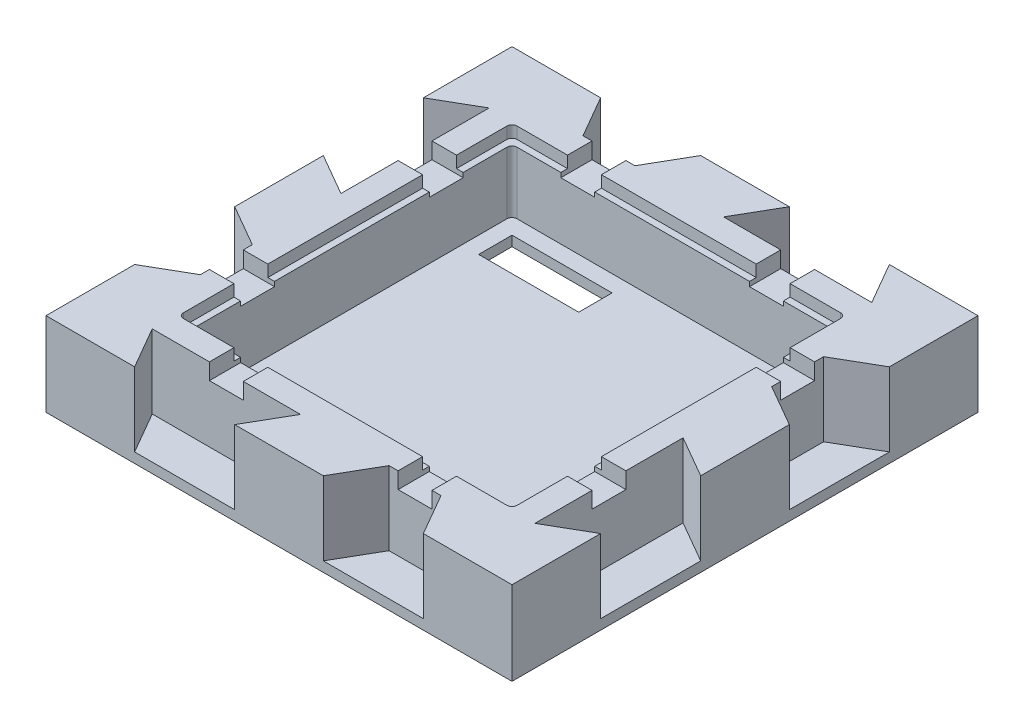
SolidWorks part; units mm, degrees
material "Macor"
ref_plane "Front Plane" through (0, 0, 0) normal (0, 0, 1) x (1, 0, 0)
ref_plane "Top Plane" through (0, 0, 0) normal (0, 1, 0) x (1, 0, 0)
ref_plane "Right Plane" through (0, 0, 0) normal (1, 0, 0) x (0, 0, -1)
sketch "Sketch1" plane through (0, 0, 0) normal (0, 1, 0) x (1, 0, 0)
  line L1 (-69.85, -69.85) -> (69.85, -69.85)
  line L2 (-69.85, -69.85) -> (-69.85, 69.85)
  line L3 (-69.85, 69.85) -> (69.85, 69.85)
  line L4 (69.85, -69.85) -> (69.85, 69.85)
  line L5 (-69.85, -69.85) -> (69.85, 69.85) construction
  line L6 (-69.85, 69.85) -> (69.85, -69.85) construction
  point P0 (0, 0)
  dimension "D1" = 139.7
extrude "Boss-Extrude1" add sketch "Sketch1" along normal mid plane 25.4
sketch "Sketch2" plane through (0, 12.7, 0) normal (0, 1, 0) x (1, 0, 0)
  line L0 (69.85, -69.85) -> (69.85, 69.85) construction
  line L1 (-69.85, -69.85) -> (69.85, -69.85)
  line L2 (-69.85, -69.85) -> (-69.85, 69.85)
  line L3 (-69.85, 69.85) -> (69.85, 69.85)
  line L4 (69.85, -69.85) -> (69.85, 69.85)
  line L5 (-69.85, -69.85) -> (69.85, 69.85) construction
  line L6 (-69.85, 69.85) -> (69.85, -69.85) construction
  point P0 (0, 0)
  dimension "D1" = 0
extrude "Cut-Extrude1" cut sketch "Sketch2" against normal offset from surface (0.3 mm away) 0.3 up to face at (0, 12.7, 0)
sketch "Sketch4" plane through (0, 12.4, 0) normal (0, 1, 0) x (1, 0, 0)
  line L0 (-43.2833, -69.85) -> (-50.5002, -57.35)
  line L2 (-50.5002, -57.35) -> (-6.0665, -57.35)
  line L3 (-6.0665, -57.35) -> (-13.2833, -69.85)
  line L4 (-13.2833, -69.85) -> (-43.2833, -69.85)
  line L5 (43.2833, -69.85) -> (36.0665, -57.35)
  line L24 (43.2833, -69.85) -> (13.2833, -69.85)
  line L25 (-69.85, -69.85) -> (-43.2833, -69.85) construction
  line L26 (-13.2833, -69.85) -> (13.2833, -69.85) construction
  line L27 (43.2833, -69.85) -> (69.85, -69.85) construction
  line L28 (36.0665, -57.35) -> (20.5002, -57.35)
  line L30 (13.2833, -69.85) -> (20.5002, -57.35)
  line L31 (-69.85, 69.85) -> (-69.85, -69.85) construction
  line L32 (69.85, -69.85) -> (69.85, 69.85) construction
  line L33 (-69.85, -69.85) -> (69.85, -69.85) construction
  point P2 (0, 0)
  point P3 (13.2833, -69.85)
  point P7 (0, 0)
  point P11 (0, 0)
  point P12 (0, 0)
  point P13 (0, 0)
  point P14 (-78.8839, -69.85)
  point P19 (0, 0)
  point P22 (80.709, -69.0975)
  point P25 (0, 0)
  dimension "D2" = 30
  dimension "D1" = 60
  dimension "D3" = 12.5
  dimension "D4" = 60
extrude "Cut-Extrude2" cut sketch "Sketch4" against normal offset from surface 3 and the other way through all up to face at (0, -12.7, 0)
sketch "Sketch18" plane through (0, 0, 57.35) normal (0, 0, 1) x (1, 0, 0)
  line L1 (0, -13.805) -> (0, 13.805) construction
  line L3 (23.2033, 12.4) -> (23.2033, 7.525)
  line L4 (23.2033, 7.525) -> (33.3633, 7.525)
  line L5 (33.3633, 12.4) -> (33.3633, 7.525)
  line L6 (-23.2033, 12.4) -> (-33.3633, 12.4)
  line L7 (-33.3633, 12.4) -> (-33.3633, 7.525)
  line L8 (-23.2033, 12.4) -> (-23.2033, 7.525)
  line L9 (-23.2033, 7.525) -> (-33.3633, 7.525)
  line L10 (23.2033, 12.4) -> (33.3633, 12.4)
  line L11 (20.5002, 12.4) -> (36.0665, 12.4) construction
  point P7 (28.2833, 12.4)
  point P14 (28.2833, 12.4)
  dimension "D1" = 10.16
  dimension "D2" = 4.875
extrude "Cut-Extrude6" cut sketch "Sketch18" against normal blind 20
ref_axis "Axis1" through (0, 29.6009, 0) along (0, -1, 0)
pattern_circular "CirPattern1" count 4 over 360 about axis through (0, 29.6009, 0) along (0, -1, 0) of "Cut-Extrude2", "Cut-Extrude6"
sketch "Sketch19" plane through (0, 12.4, 0) normal (0, 1, 0) x (1, 0, 0)
  line L1 (-50, -50) -> (50, -50)
  line L2 (-50, -50) -> (-50, 50)
  line L3 (-50, 50) -> (50, 50)
  line L4 (50, -50) -> (50, 50)
  line L5 (-50, -50) -> (50, 50) construction
  line L6 (-50, 50) -> (50, -50) construction
  point P0 (0, 0)
  dimension "D1" = 100
extrude "Cut-Extrude8" cut sketch "Sketch19" against normal blind 3.5
sketch "Sketch20" plane through (0, 8.9, 0) normal (0, 1, 0) x (1, 0, 0)
  line L1 (-48, -48) -> (48, -48)
  line L2 (-48, -48) -> (-48, 48)
  line L3 (-48, 48) -> (48, 48)
  line L4 (48, -48) -> (48, 48)
  line L5 (-48, -48) -> (48, 48) construction
  line L6 (-48, 48) -> (48, -48) construction
  point P0 (0, 0)
  dimension "D1" = 96
extrude "Cut-Extrude9" cut sketch "Sketch20" against normal blind 18.6
sketch "Sketch21" plane through (0, -9.7, 0) normal (0, 1, 0) x (1, 0, 0)
  line L0 (-48, 48) -> (-48, -48) construction
  line L1 (-13, 33) -> (-43, 33)
  line L2 (-13, 33) -> (-13, 43)
  line L3 (-13, 43) -> (-43, 43)
  line L4 (-43, 33) -> (-43, 43)
  line L5 (48, 48) -> (-48, 48) construction
  dimension "D1" = 30
  dimension "D2" = 10
  dimension "D3" = 5
  dimension "D4" = 5
extrude "Cut-Extrude10" cut sketch "Sketch21" against normal through all
fillet "Fillet2" radius 1.5 8 edges at (-50, 10.65, -50) (-50, 10.65, 50) (50, 10.65, 50) (50, 10.65, -50) (48, -0.4, 48) (-48, -0.4, 48) (-48, -0.4, -48) (48, -0.4, -48)
sketch "Sketch22" plane through (0, -12.7, 0) normal (0, -1, 0) x (1, 0, 0)
  line L1 (69.85, -69.85) -> (-69.85, -69.85) construction
  line L2 (-69.85, 69.85) -> (-49.85, 69.85)
  line L3 (-69.85, 69.85) -> (-69.85, -69.85)
  line L4 (-69.85, -69.85) -> (-49.85, -69.85)
  line L5 (-49.85, 69.85) -> (-49.85, -69.85)
  line L7 (69.85, 69.85) -> (49.85, 69.85)
  line L8 (69.85, 69.85) -> (69.85, -69.85)
  line L9 (69.85, -69.85) -> (49.85, -69.85)
  line L10 (49.85, 69.85) -> (49.85, -69.85)
  dimension "D1" = 20
split line "Split Line1"
pattern_circular "CirPattern2" count 2 over 360 about axis through (0, 29.6009, 0) along (0, -1, 0) of "Cut-Extrude10"
equation "\"panel_width\"= 5.5in"
equation "\"finger_joint_width\"= 30mm"
equation "\"D1@Sketch1\"=\"panel_width\""
equation "\"D2@Sketch4\"=\"finger_joint_width\""
